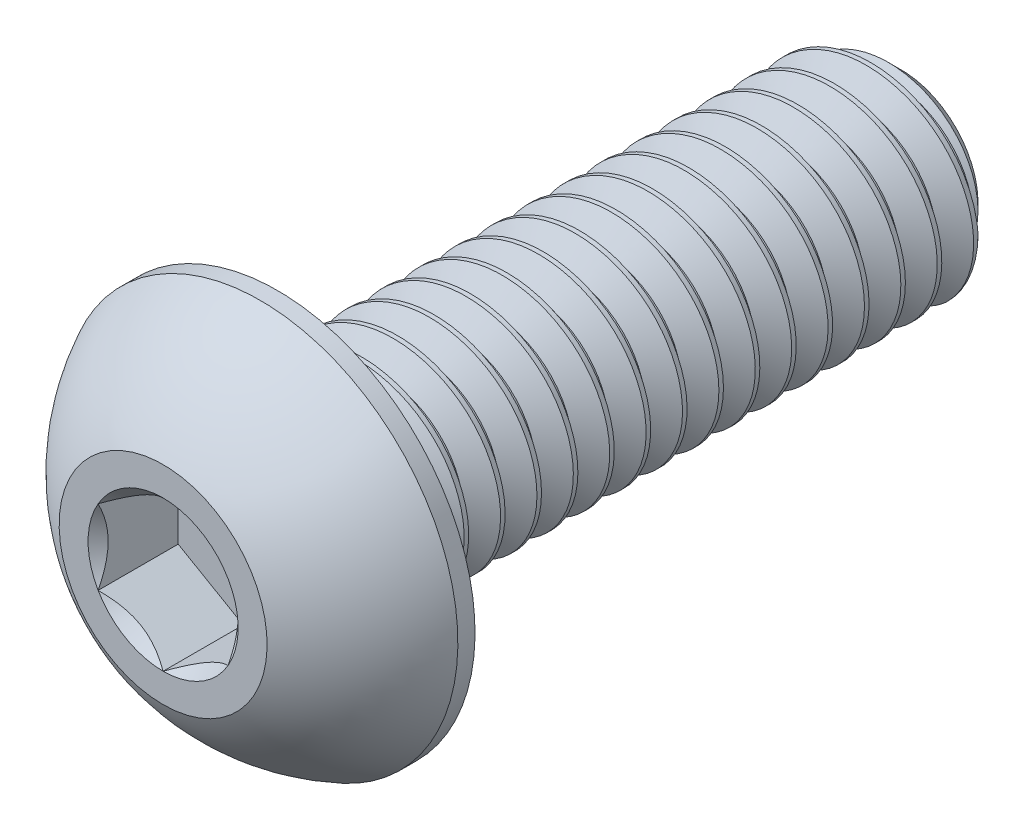
SolidWorks part; units mm, degrees
ref_plane "Front" through (0, 0, 0) normal (0, 0, 1) x (1, 0, 0)
ref_plane "Top" through (0, 0, 0) normal (0, 1, 0) x (1, 0, 0)
ref_plane "Right" through (0, 0, 0) normal (1, 0, 0) x (0, 0, -1)
sketch "Sketch1" plane through (0, 0, 0) normal (1, 0, 0) x (0, 0, -1)
  line L2 (-6, 2) -> (6, 2)
  line L3 (6, 2) -> (6, 0)
  line L4 (6, 0) -> (-6, 0)
  line L6 (-6.33, 3.8) -> (-6, 3.8) construction
  line L7 (6, 2) -> (6, -2) construction
  line L8 (-8.2, 0) -> (-6, 0) construction
  line L9 (-6, 3.8) -> (-6, -3.8) construction
  line L11 (-6, 2) -> (-6, 0)
  line L13 (-8.2, 1.25) -> (-8.2, -1.25) construction
  line L14 (-8.2, 1.25) -> (-8.2, 2) construction
  line L15 (5.9563, 2.0758) -> (6.3063, 1.4696) construction
  line L16 (6.3063, 1.4696) -> (6.6563, 2.0758) construction
  line L17 (6.6563, 2.0758) -> (5.9563, 2.0758) construction
  line L18 (6, 2) -> (6.6125, 2) construction
  line L19 (6.3063, 2.0758) -> (6.3063, 2) construction
  line L20 (6.3063, 2) -> (6.3063, 1.5453) construction
  line L21 (6.3063, 1.5453) -> (6.3063, 1.4696) construction
  line L22 (6.2625, 1.5453) -> (6.35, 1.5453)
  line L23 (5.9781, 2.0379) -> (6.6344, 2.0379)
  line L24 (6.35, 1.5453) -> (6.6344, 2.0379)
  line L25 (6.2625, 1.5453) -> (5.9781, 2.0379)
  line L26 (5.475, 2) -> (6, 1.475)
  arc A3 (-8.2, 2) -> (-6.33, 3.8) centre (-4.4736, 0) cw construction
  point P29 (6.3063, 2.0379)
  point P30 (4.25, -2)
  point P33 (0, 0)
  dimension "Thread Size" = 4
  dimension "D1" = 0.33
  dimension "Head Height" = 2.2
  dimension "Head Diameter" = 7.6
  dimension "Length" = 12
  dimension "Drive Size" = 2.5
  dimension "Thread Pitch" = 0.7
  dimension "D3" = 0.0875
  dimension "D2" = 0.525
  dimension "D4" = 45
  dimension "D5" = 1.75
sketch "Sketch10" plane through (0, 0, 0) normal (1, 0, 0) x (0, 0, -1)
  line L0 (5.475, 2) -> (6, 1.475) construction
  line L1 (5.475, 2) -> (6, 1.475)
  line L4 (6, 2) -> (-6, 2)
  line L5 (6, 0) -> (6, 2)
  line L6 (-6, 0) -> (6, 0)
  line L7 (-6, 2) -> (-6, 0)
  line L8 (5.475, 2) -> (-6, 2)
  line L9 (6, 0) -> (6, 1.475)
  line L10 (-6, 0) -> (6, 0)
  line L11 (-6, 2) -> (-6, 0)
  dimension "D1" = 0
revolve "Revolve3" add sketch "Sketch10" angle 360 about L8
sketch "Sketch7" plane through (0, 0, 0) normal (1, 0, 0) x (0, 0, -1)
  line L6 (-6.33, 3.8) -> (-6, 3.8) construction
  line L8 (-8.2, 0) -> (-6, 0) construction
  line L11 (-6, 3.8) -> (-6, -3.8) construction
  line L12 (-6.33, 3.8) -> (-6, 3.8)
  line L13 (-8.2, 0) -> (-6, 0)
  line L14 (-8.2, 1.25) -> (-8.2, -1.25) construction
  line L15 (-6, 3.8) -> (-6, 0)
  line L16 (-8.2, 2) -> (-8.2, 0)
  arc A2 (-6.33, 3.8) -> (-8.2, 2) centre (-4.4736, 0) ccw construction
  arc A3 (-6.33, 3.8) -> (-8.2, 2) centre (-4.4736, 0) ccw
revolve "Revolve2" add sketch "Sketch7" angle 360 mid plane about L13
sketch "Sketch5" plane through (0, 0, 8.2) normal (0, 0, 1) x (1, 0, 0)
  line L1 (1.25, -0.7217) -> (1.25, 0.7217)
  line L2 (1.25, 0.7217) -> (0, 1.4434)
  line L3 (0, 1.4434) -> (-1.25, 0.7217)
  line L4 (-1.25, 0.7217) -> (-1.25, -0.7217)
  line L5 (-1.25, -0.7217) -> (0, -1.4434)
  line L6 (0, -1.4434) -> (1.25, -0.7217)
  circle A0 centre (0, 0) radius 1.25 construction
extrude "Cut-Extrude2" cut sketch "Sketch5" against normal blind 1.54
sketch "Sketch6" plane through (0, 0, 8.2) normal (0, 0, 1) x (1, 0, 0)
  circle A0 centre (0, 0) radius 1.4434
extrude "Cut-Extrude3" cut sketch "Sketch6" against normal blind 1.54 draft 45
sketch "Sketch9" plane through (0, 0, 6) normal (0, 0, -1) x (-1, 0, 0)
  circle A0 centre (0, 0) radius 2 construction
  circle A4 centre (0, 0) radius 2
split "Split1" bodies to split 113 resulting bodies 123 124 split by face at (0, -3.8, 6)
sketch "Sketch11" plane through (0, 0, -6) normal (0, 0, -1) x (-1, 0, 0)
  circle A0 centre (0, 0) radius 2 construction
  circle A1 centre (0, 0) radius 2
curve "Helix/Spiral1" pitch 0.7 height 14.2 radius 2 centre (0, 0, -6) axis (0, 0, 1) start towards (0, 1, 0)
sketch "Sketch12" plane through (0, 0, 0) normal (1, 0, 0) x (0, 0, -1)
  line L0 (6.2625, 1.5453) -> (6.35, 1.5453) construction
  line L1 (6.35, 1.5453) -> (6.6344, 2.0379) construction
  line L2 (5.9781, 2.0379) -> (6.6344, 2.0379) construction
  line L3 (6.2625, 1.5453) -> (5.9781, 2.0379) construction
  line L4 (6.2625, 1.5453) -> (6.35, 1.5453)
  line L5 (6.35, 1.5453) -> (6.6344, 2.0379)
  line L6 (5.9781, 2.0379) -> (6.6344, 2.0379)
  line L7 (6.2625, 1.5453) -> (5.9781, 2.0379)
sweep "Cut-Sweep2" cut profiles "Sketch12" path "Helix/Spiral1" align with end faces yes
extrude "Boss-Extrude1" add sketch "Sketch9" along normal blind 10 draft 45
equation "\"D1@Cut-Extrude2\" = \"Head Height@Sketch1\" * .7"
equation "\"D1@Sketch1\" = \"Head Height@Sketch1\" * .15"
equation "\"D1@Cut-Extrude3\" = \"D1@Cut-Extrude2\""
equation "\"D3@Sketch1\" = \"Thread Pitch@Sketch1\" / 8"
equation "\"D2@Sketch1\" = \"Thread Pitch@Sketch1\" * 0.75"
equation "\"D3@Helix/Spiral1\" = \"Length@Sketch1\" + \"Head Height@Sketch1\""
equation "\"D4@Helix/Spiral1\" = \"Thread Pitch@Sketch1\""
equation "\"D5@Sketch1\" = \"Thread Pitch@Sketch1\" * 2.5"
